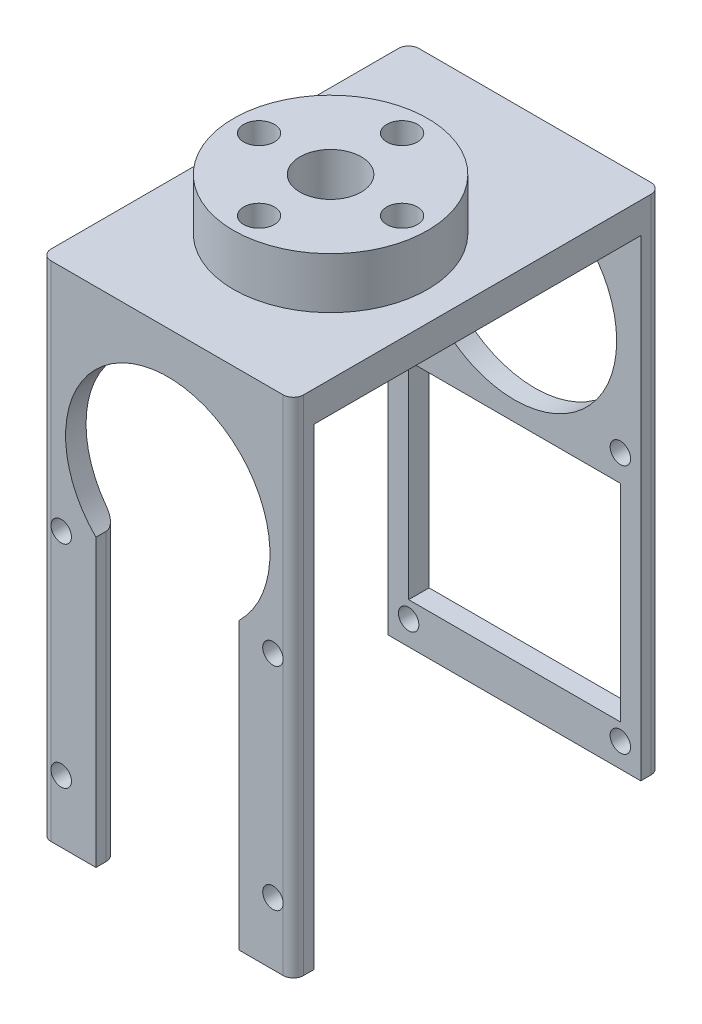
SolidWorks part; units mm, degrees
ref_plane "前视基准面" through (0, 0, 0) normal (0, 0, 1) x (1, 0, 0)
ref_plane "上视基准面" through (0, 0, 0) normal (0, 1, 0) x (1, 0, 0)
ref_plane "右视基准面" through (0, 0, 0) normal (1, 0, 0) x (0, 0, -1)
sketch "草图1" plane through (0, 0, 0) normal (0, 0, 1) x (1, 0, 0)
  line L1 (0, 0) -> (24.72, 0)
  line L2 (0, 0) -> (0, 49.22)
  line L3 (0, 49.22) -> (24.72, 49.22)
  line L4 (24.72, 0) -> (24.72, 49.22)
  dimension "D1" = 24.72
  dimension "D2" = 49.22
extrude "凸台-拉伸1" add sketch "草图1" along normal blind 36
sketch "草图3" plane through (0, 0, 0) normal (0, -1, 0) x (1, 0, 0)
  line L0 (0, 0) -> (24.72, 0) construction
  line L1 (0, 34) -> (24.72, 34)
  line L2 (0, 34) -> (0, 2)
  line L3 (0, 2) -> (24.72, 2)
  line L4 (24.72, 34) -> (24.72, 2)
  line L5 (24.72, 36) -> (24.72, 0) construction
  line L7 (0, 36) -> (24.72, 36) construction
  dimension "D1" = 2
  dimension "D2" = 2
  dimension "D3" = 24.72
  dimension "D4" = 0
extrude "切除-拉伸1" cut sketch "草图3" against normal blind 46.22
sketch "草图4" plane through (0, 0, 2) normal (0, 0, 1) x (1, 0, 0)
  line L0 (24.72, 0) -> (24.72, 49.22) construction
  line L1 (0, 49.22) -> (0, 0) construction
  line L2 (0, 0) -> (24.72, 0) construction
  line L3 (24.72, 49.22) -> (0, 49.22) construction
  line L5 (2, 24.22) -> (22.72, 24.22)
  line L6 (2, 24.22) -> (2, 4)
  line L7 (2, 4) -> (22.72, 4)
  line L8 (22.72, 24.22) -> (22.72, 4)
  circle A0 centre (2, 2.36) radius 1
  circle A1 centre (22.72, 2.36) radius 1
  circle A2 centre (22.72, 26.81) radius 1
  circle A3 centre (2, 26.81) radius 1
  circle A4 centre (12.36, 36.11) radius 10
  dimension "D1" = 2
  dimension "D2" = 2
  dimension "D3" = 2
  dimension "D4" = 2
  dimension "D5" = 20
  dimension "D6" = 2
  dimension "D7" = 2
  dimension "D8" = 2
  dimension "D9" = 2
  dimension "D10" = 2.36
  dimension "D11" = 2.36
  dimension "D12" = 24.45
  dimension "D13" = 24.45
  dimension "D14" = 12.36
  dimension "D15" = 13.11
  dimension "D16" = 2
  dimension "D17" = 2
  dimension "D18" = 4
  dimension "D19" = 25
extrude "切除-拉伸2" cut sketch "草图4" against normal blind 2
sketch "草图6" plane through (0, 0, 36) normal (0, 0, 1) x (1, 0, 0)
  line L0 (0, 0) -> (24.72, 0) construction
  line L1 (5.4, 28) -> (19.4, 28)
  line L2 (5.4, 28) -> (5.4, 0)
  line L3 (5.4, 0) -> (19.4, 0)
  line L4 (19.4, 28) -> (19.4, 0)
  line L5 (0, 49.22) -> (0, 0) construction
  line L6 (24.72, 0) -> (24.72, 49.22) construction
  circle A0 centre (2, 6.11) radius 1
  circle A1 centre (22.72, 6.11) radius 1
  circle A2 centre (22.72, 26.81) radius 1
  circle A3 centre (2, 26.81) radius 1
  circle A4 centre (12.4284, 35.11) radius 10
  line M7 (0, 0) -> (24.72, 0)
  dimension "D1" = 2
  dimension "D2" = 2
  dimension "D3" = 2
  dimension "D4" = 2
  dimension "D5" = 20
  dimension "D6" = 2
  dimension "D7" = 6.11
  dimension "D8" = 6.11
  dimension "D9" = 2
  dimension "D10" = 2
  dimension "D11" = 20.7
  dimension "D12" = 20.7
  dimension "D13" = 2
  dimension "D14" = 35.11
  dimension "D15" = 14
  dimension "D16" = 5.32
  dimension "D17" = 28
extrude "切除-拉伸3" cut sketch "草图6" against normal blind 6 contours L4 A4 L2 L1 | A4 L2 L4 M7 | A3 | A1 | L2 A4 L4 L1 | A0 | A2 region at (12.4285, 35.92, 36) region at (12.428, 26.8283, 36) region at (12.3978, 13.0136, 36) region at (22.72, 6.11, 36) region at (2, 26.81, 36)
sketch "草图7" plane through (0, 49.22, 0) normal (0, 1, 0) x (1, 0, 0)
  line L0 (24.72, 0) -> (0, 0) construction
  line L1 (24.72, -36) -> (0, -36) construction
  line L2 (24.72, -36) -> (24.72, 0) construction
  circle A0 centre (12.36, -20) radius 9.5
  dimension "D1" = 19
  dimension "D2" = 20
  dimension "D3" = 36
  dimension "D4" = 12.36
extrude "凸台-拉伸2" add sketch "草图7" along normal blind 5
sketch "草图8" plane through (0, 54.22, 0) normal (0, 1, 0) x (1, 0, 0)
  line L0 (0, -36) -> (0, 0) construction
  line L2 (24.72, 0) -> (0, 0) construction
  line L4 (24.72, -36) -> (24.72, 0) construction
  circle A0 centre (12.36, -13) radius 1.5
  circle A1 centre (12.36, -27) radius 1.5
  circle A2 centre (19.36, -20) radius 1.5
  circle A3 centre (5.36, -20) radius 1.5
  dimension "D1" = 3
  dimension "D2" = 3
  dimension "D3" = 3
  dimension "D4" = 3
  dimension "D5" = 12.36
  dimension "D6" = 12.36
  dimension "D9" = 14
  dimension "D10" = 14
  dimension "D11" = 13
  dimension "D12" = 5.36
  dimension "D7" = 20
  dimension "D8" = 20
extrude "切除-拉伸4" cut sketch "草图8" against normal blind 8
fillet "圆角5" radius 1 1 edges at (0, 24.61, 36)
fillet "圆角6" radius 1 1 edges at (24.72, 24.61, 36)
fillet "圆角7" radius 1 1 edges at (0, 24.61, 0)
fillet "圆角8" radius 1 1 edges at (24.72, 24.61, 0)
fillet "圆角9" radius 1 1 edges at (19.4, 13.9704, 34)
fillet "圆角10" radius 1 1 edges at (5.4, 13.9983, 34)
sketch "草图9" plane through (0, 54.22, 0) normal (0, 1, 0) x (1, 0, 0)
  circle A0 centre (12.36, -20) radius 3
  circle A1 centre (12.36, -20) radius 9.5 construction
  dimension "D1" = 0
  dimension "D2" = 6
extrude "切除-拉伸5" cut sketch "草图9" against normal blind 10
sketch "草图10" plane through (0, 46.22, 0) normal (0, -1, 0) x (1, 0, 0)
  circle A0 centre (12.36, 27) radius 3
  circle A1 centre (5.36, 20) radius 3
  circle A2 centre (12.36, 13) radius 3
  circle A3 centre (19.36, 20) radius 3
  dimension "D1" = 6
  dimension "D2" = 6
  dimension "D3" = 6
  dimension "D4" = 6
extrude "切除-拉伸6" cut sketch "草图10" against normal blind 2
